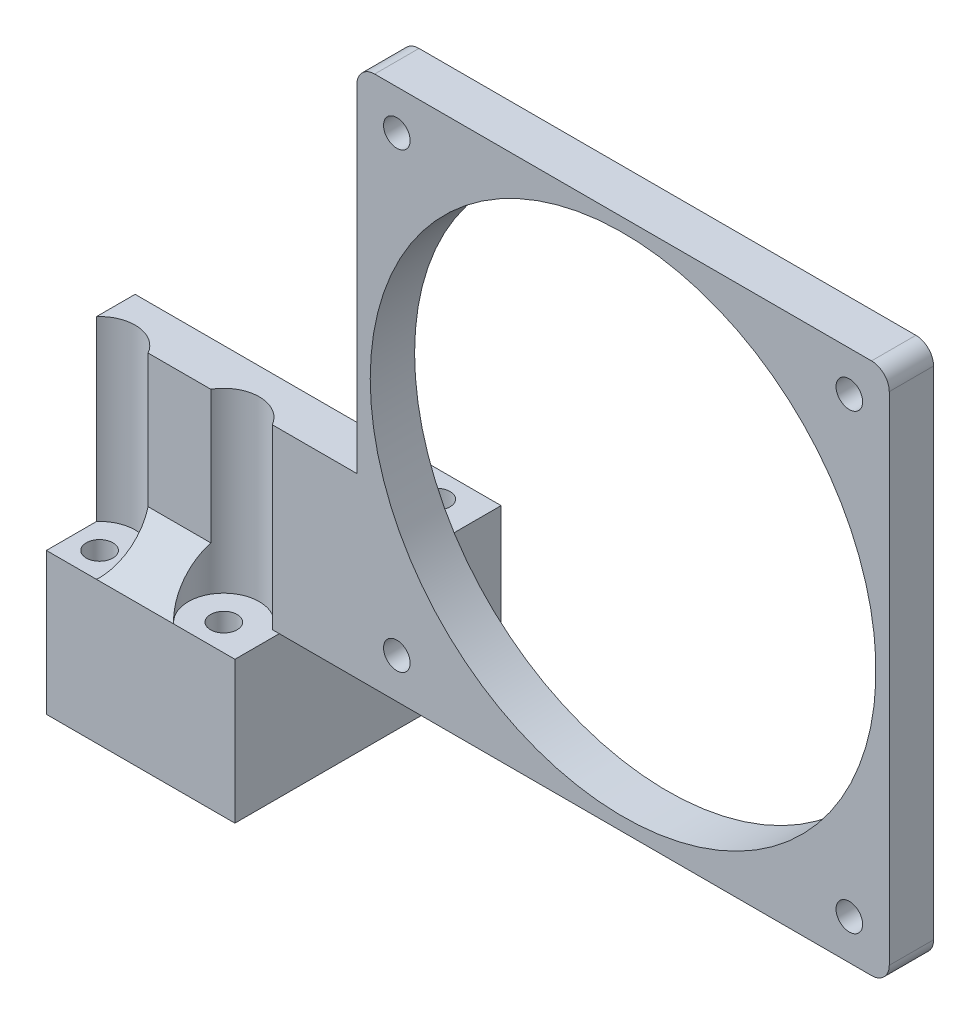
SolidWorks part; units mm, degrees
ref_plane "前视基准面" through (0, 0, 0) normal (0, 0, 1) x (1, 0, 0)
ref_plane "上视基准面" through (0, 0, 0) normal (0, 1, 0) x (1, 0, 0)
ref_plane "右视基准面" through (0, 0, 0) normal (1, 0, 0) x (0, 0, -1)
other "Configuration Table"
sketch "草图1" plane through (0, 0, 0) normal (0, 0, 1) x (1, 0, 0)
  line L1 (0, 0) -> (-60, 0)
  line L2 (0, 0) -> (0, 60)
  line L3 (0, 60) -> (-60, 60)
  line L4 (-60, 0) -> (-60, 60)
  dimension "D1" = 60
  dimension "D2" = 60
extrude "凸台-拉伸1" add sketch "草图1" along normal blind 5
sketch "草图2" plane through (0, 0, 0) normal (0, 0, -1) x (-1, 0, 0)
  line L0 (0, 0) -> (0, 60) construction
  line L1 (0, 60) -> (60, 60) construction
  circle A0 centre (4.5, 55.5) radius 1.5
  circle A1 centre (55.5, 55.5) radius 1.5
  circle A2 centre (4.5, 4.5) radius 1.5
  circle A3 centre (55.5, 4.5) radius 1.5
  dimension "D1" = 51
  dimension "D2" = 51
  dimension "D3" = 51
  dimension "D4" = 51
  dimension "D5" = 4.5
  dimension "D6" = 4.5
  dimension "D7" = 4.5
  dimension "D8" = 4.5
  dimension "D9" = 3
extrude "切除-拉伸1" cut sketch "草图2" against normal blind 5
sketch "草图3" plane through (0, 0, 0) normal (0, 0, -1) x (-1, 0, 0)
  line L0 (30, 60) -> (30, -2.4653) construction
  line L5 (0, 60) -> (60, 60) construction
  line L6 (0, 30) -> (70.1164, 30) construction
  line L7 (0, 0) -> (0, 60) construction
  circle A2 centre (30, 30) radius 28.5
  dimension "D1" = 57
extrude "切除-拉伸2" cut sketch "草图3" against normal blind 5
sketch "草图4" plane through (-60, 0, 0) normal (-1, 0, 0) x (0, 0, 1)
  line L1 (0, 0) -> (5, 0)
  line L2 (0, 0) -> (0, 20)
  line L3 (0, 20) -> (5, 20)
  line L4 (5, 0) -> (5, 20)
  dimension "D1" = 20
extrude "凸台-拉伸2" add sketch "草图4" along normal blind 30
sketch "草图5" plane through (0, 0, 0) normal (0, -1, 0) x (1, 0, 0)
  line L1 (-90, 10) -> (-68.75, 10)
  line L2 (-90, 10) -> (-90, -20)
  line L3 (-90, -20) -> (-68.75, -20)
  line L4 (-68.75, 10) -> (-68.75, -20)
  line L5 (-90, 0) -> (-90, 5) construction
  line L6 (-90, 0) -> (0, 0) construction
  dimension "D1" = 21.25
  dimension "D2" = 20
  dimension "D3" = 30
  dimension "D4" = 0
extrude "凸台-拉伸3" add sketch "草图5" along normal blind 16
sketch "草图6" plane through (0, -16, 0) normal (0, -1, 0) x (1, 0, 0)
  line L0 (-68.75, 10) -> (-90, 10) construction
  line L1 (-90, 10) -> (-90, -20) construction
  line L3 (-90, -20) -> (-68.75, -20) construction
  circle A0 centre (-87, 7) radius 1.5
  circle A1 centre (-73, 7) radius 1.5
  circle A2 centre (-87, -17) radius 1.5
  circle A3 centre (-73, -17) radius 1.5
  dimension "D1" = 3
  dimension "D2" = 3
  dimension "D3" = 14
  dimension "D4" = 14
  dimension "D7" = 3
  dimension "D8" = 3
  dimension "D9" = 3
extrude "切除-拉伸3" cut sketch "草图6" against normal blind 30
sketch "草图7" plane through (0, 0, 0) normal (0, 1, 0) x (1, 0, 0)
  circle A2 centre (-87, -7) radius 4
  circle A3 centre (-73, -7) radius 4
  dimension "D1" = 8
  dimension "D2" = 8
extrude "切除-拉伸4" cut sketch "草图7" along normal blind 30
chamfer "倒角1" distance 10 angle 45 1 edges at (-79.375, 0, 0)
chamfer "倒角2" distance 5 angle 45 1 edges at (-80, 0, 5)
fillet "圆角1" radius 2 3 edges at (0, 0, 2.5) (-60, 60, 2.5) (0, 60, 2.5)
